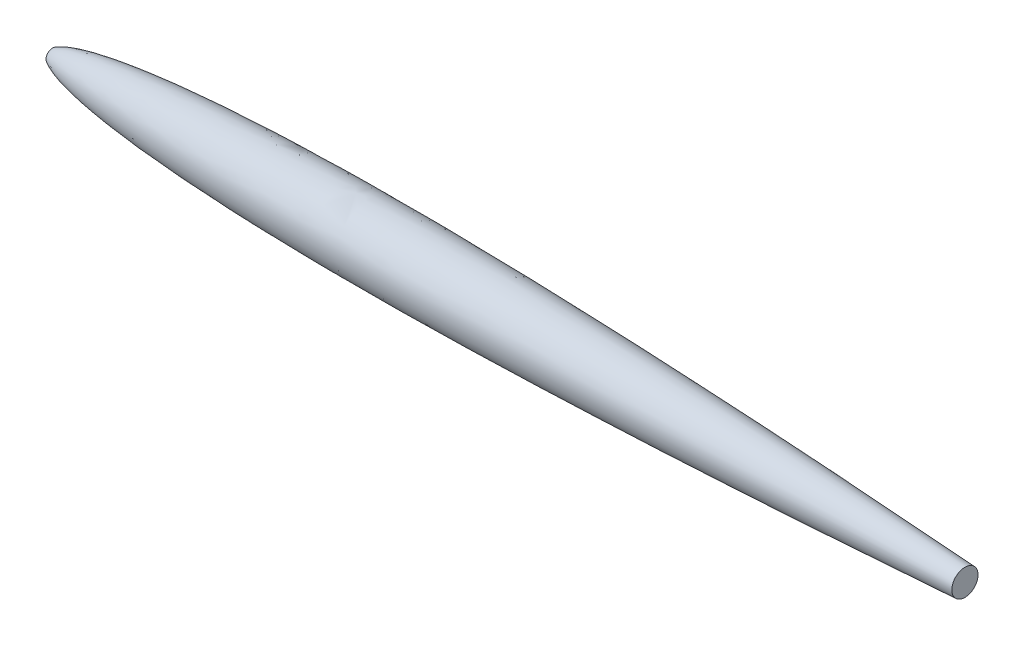
SolidWorks part; units mm, degrees
ref_plane "Front Plane" through (0, 0, 0) normal (0, 0, 1) x (1, 0, 0)
ref_plane "Top Plane" through (0, 0, 0) normal (0, 1, 0) x (1, 0, 0)
ref_plane "Right Plane" through (0, 0, 0) normal (1, 0, 0) x (0, 0, -1)
sketch "rootSketch" plane through (0, 0, 0) normal (0, 1, 0) x (1, 0, 0)
  line L0 (0, 0) -> (12000, 0) construction
  line L1 (2750, -330) -> (2750, 330) construction
  line L2 (0, 0) -> (11000, 0)
  spline S0 degree 4 poles (0, 0) (0.0002, 1.4166) (0.1225, 4.2408) (0.6739, 8.4547) (2.1097, 13.9385) (4.13, 19.1147) (6.6109, 23.9643) (9.9914, 29.3681) (13.8074, 34.3715) (18.0051, 39.0824) (24.0066, 45.0125) (32.3839, 52.2354) (43.384, 60.1944) (57.0761, 68.6181) (73.983, 77.7243) (92.7893, 86.6435) (113.9578, 95.5167) (137.4556, 104.3111) (166.2995, 114.136) (201.291, 124.8338) (243.0702, 136.2047) (291.673, 147.964) (341.2433, 158.778) (390.608, 168.603) (439.7192, 177.609) (500.6517, 187.9807) (573.4692, 199.2826) (658.6122, 211.1866) (758.0842, 223.6079) (859.6848, 234.9957) (963.387, 245.4645) (1069.1706, 255.1028) (1175.0326, 263.8354) (1280.9578, 271.7615) (1386.9346, 278.9616) (1492.954, 285.5022) (1625.577, 292.9263) (1784.8272, 300.7239) (1970.7211, 308.3762) (2183.2661, 315.3874) (2395.8558, 320.8604) (2608.4762, 324.9557) (2821.1167, 327.8069) (3033.7692, 329.5269) (3299.5919, 330.3841) (3618.5808, 329.5138) (3990.7204, 326.0523) (4415.9852, 319.2091) (4841.2016, 309.8574) (5266.3634, 298.3074) (5691.4677, 284.8151) (6116.5132, 269.5907) (6541.4998, 252.8057) (6966.4276, 234.5973) (7391.2968, 215.0715) (7816.1072, 194.3061) (8187.764, 175.0965) (8506.2884, 157.9049) (8771.6988, 143.0951) (8984.0106, 130.9561) (9196.3055, 118.5234) (9382.048, 107.3844) (9541.2445, 97.6474) (9673.9002, 89.4049) (9780.02, 82.7331) (9912.6633, 74.2947) (10032.035, 66.5803) (10138.1364, 59.6277) (10230.971, 53.4713) (10284.0168, 49.9324) (10337.0641, 46.3721) (10390.1043, 42.7909) (10443.153, 39.1874) (10496.1834, 35.5635) (10549.2402, 31.9155) (10602.2495, 28.2488) (10655.3329, 24.5543) (10708.2897, 20.8463) (10761.4536, 17.1004) (10814.2582, 13.3575) (10861.0394, 10.0201) (10900.2084, 7.2123) (10934.3368, 4.7545) (10958.871, 2.9835) (10991.7181, 0.6028) (11015.0262, -1.0918) (11049.9588, -3.6388) (11071.8096, -5.2409) (11099.5819, -7.2784) (11124.1625, -9.0892) (11155.0411, -11.3693) (11188.9639, -13.8862) (11223.5859, -16.4645) (11266.4367, -19.6696) (11318.0968, -23.5545) (11369.6077, -27.4555) (11421.2086, -31.3904) (11472.7604, -35.3439) (11524.3346, -39.3212) (11584.4862, -43.9929) (11670.4236, -50.7243) (11756.3495, -57.532) (11842.2728, -64.4184) (11928.1873, -71.3847) (11996.9163, -77.0066) (12048.459, -81.2601) (12082.8201, -84.1126) (12100, -85.543) knots 0 0 0 0 0 0.000464 0.000929 0.001393 0.001858 0.002287 0.002716 0.003486 0.003922 0.004359 0.005488 0.007118 0.008378 0.009638 0.011797 0.013955 0.015919 0.017882 0.02181 0.025978 0.030146 0.034314 0.038482 0.042518 0.046554 0.054626 0.062698 0.07077 0.079497 0.088224 0.096952 0.105679 0.114406 0.123133 0.13186 0.140587 0.158059 0.17553 0.193002 0.210474 0.227946 0.245418 0.26289 0.280362 0.315306 0.35025 0.385194 0.420137 0.455081 0.490025 0.524969 0.559913 0.594857 0.6298 0.664744 0.699688 0.71716 0.734632 0.752104 0.769576 0.787048 0.795784 0.80452 0.813256 0.821992 0.839464 0.843832 0.8482 0.852567 0.856935 0.861303 0.865671 0.870039 0.874407 0.878775 0.883143 0.887511 0.891879 0.896247 0.900615 0.902799 0.904983 0.907167 0.909351 0.912184 0.915017 0.916433 0.91785 0.920682 0.923515 0.926348 0.929181 0.932013 0.937679 0.943345 0.946177 0.94901 0.954676 0.960341 0.966007 0.977338 0.983003 0.988669 0.994334 1 1 1 1 1 construction
  spline S1 degree 4 poles (0, 0) (0.0002, 1.4166) (0.1225, 4.2408) (0.6739, 8.4547) (2.1097, 13.9385) (4.13, 19.1147) (6.6109, 23.9643) (9.9914, 29.3681) (13.8074, 34.3715) (18.0051, 39.0824) (24.0066, 45.0125) (32.3839, 52.2354) (43.384, 60.1944) (57.0761, 68.6181) (73.983, 77.7243) (92.7893, 86.6435) (113.9578, 95.5167) (137.4556, 104.3111) (166.2995, 114.136) (201.291, 124.8338) (243.0702, 136.2047) (291.673, 147.964) (341.2433, 158.778) (390.608, 168.603) (439.7192, 177.609) (500.6517, 187.9807) (573.4692, 199.2826) (658.6122, 211.1866) (758.0842, 223.6079) (859.6848, 234.9957) (963.387, 245.4645) (1069.1706, 255.1028) (1175.0326, 263.8354) (1280.9578, 271.7615) (1386.9346, 278.9616) (1492.954, 285.5022) (1625.577, 292.9263) (1784.8272, 300.7239) (1970.7211, 308.3762) (2183.2661, 315.3874) (2395.8558, 320.8604) (2608.4762, 324.9557) (2821.1167, 327.8069) (3033.7692, 329.5269) (3299.5919, 330.3841) (3618.5808, 329.5138) (3990.7204, 326.0523) (4415.9852, 319.2091) (4841.2016, 309.8574) (5266.3634, 298.3074) (5691.4677, 284.8151) (6116.5132, 269.5907) (6541.4998, 252.8057) (6966.4276, 234.5973) (7391.2968, 215.0715) (7816.1072, 194.3061) (8187.764, 175.0965) (8506.2884, 157.9049) (8771.6988, 143.0951) (8984.0106, 130.9561) (9196.3055, 118.5234) (9382.048, 107.3844) (9541.2445, 97.6474) (9673.9002, 89.4049) (9780.02, 82.7331) (9912.6633, 74.2947) (10032.035, 66.5803) (10138.1364, 59.6277) (10230.971, 53.4713) (10284.0168, 49.9324) (10337.0641, 46.3721) (10390.1043, 42.7909) (10443.153, 39.1874) (10496.1834, 35.5635) (10549.2402, 31.9155) (10602.2495, 28.2488) (10655.3329, 24.5543) (10708.2897, 20.8463) (10761.4536, 17.1004) (10814.2582, 13.3575) (10861.0394, 10.0201) (10900.2084, 7.2123) (10934.3368, 4.7545) (10958.871, 2.9835) (10981.8033, 1.3214) (10993.9727, 0.438) (11000, 0) knots 0 0 0 0 0 0.000464 0.000929 0.001393 0.001858 0.002287 0.002716 0.003486 0.003922 0.004359 0.005488 0.007118 0.008378 0.009638 0.011797 0.013955 0.015919 0.017882 0.02181 0.025978 0.030146 0.034314 0.038482 0.042518 0.046554 0.054626 0.062698 0.07077 0.079497 0.088224 0.096952 0.105679 0.114406 0.123133 0.13186 0.140587 0.158059 0.17553 0.193002 0.210474 0.227946 0.245418 0.26289 0.280362 0.315306 0.35025 0.385194 0.420137 0.455081 0.490025 0.524969 0.559913 0.594857 0.6298 0.664744 0.699688 0.71716 0.734632 0.752104 0.769576 0.787048 0.795784 0.80452 0.813256 0.821992 0.839464 0.843832 0.8482 0.852567 0.856935 0.861303 0.865671 0.870039 0.874407 0.878775 0.883143 0.887511 0.891879 0.896247 0.900615 0.902799 0.904983 0.907167 0.909351 0.909351 0.909351 0.909351 0.909351
  point P5 (2750, 0)
  dimension "rootQuarterChord" = 2750
  dimension "rootMaxThickness" = 660
revolve "Revolve1" add sketch "rootSketch" angle 360 about L0
ref_plane "Plane1" through (9020, 0, 0) normal (1, 0, 0) x (0, 0, -1)
sketch "cutSketch" plane through (9020, 0, 0) normal (1, 0, 0) x (0, 0, -1)
  circle A0 centre (0, 0) radius 330
  dimension "cutDiameter" = 660
extrude "Cut-Extrude1" cut sketch "cutSketch" along normal through all
sketch "Sketch1" plane through (0, 0, 0) normal (1, 0, 0) x (0, 0, -1)
  circle A0 centre (0, 0) radius 330
  dimension "D1" = 660
extrude "Cut-Extrude2" cut sketch "Sketch1" along normal blind 50 contours A0
equation "\"chord\"= 11.00"
equation "\"NACAairfoil\"= 0006"
equation "\"tailCutoffPercentage\"= 0.18"
equation "\"rootQuarterChord@rootSketch\"=\"chord\"/4"
equation "\"rootMaxThickness@rootSketch\"= \"rootQuarterChord@rootSketch\" * 4 * \"NACAairfoil\" / 100"
equation "\"cutDiameter@cutSketch\"=\"rootMaxThickness@rootSketch\""
equation "\"cutChord@Plane1\"= \"rootQuarterChord@rootSketch\" * 4 * ( 1 - \"tailCutoffPercentage\" )"
equation "\"D1@Sketch1\"=\"rootMaxThickness@rootSketch\""
